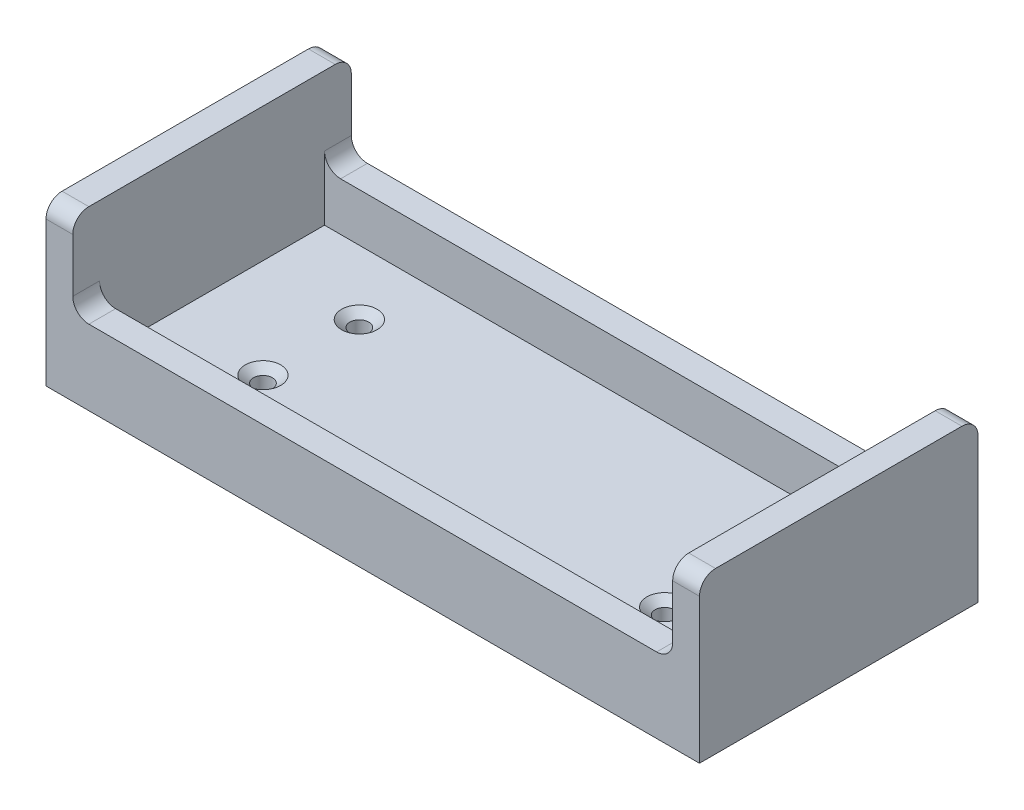
SolidWorks part; units mm, degrees
material "PET"
ref_plane "Front Plane" through (0, 0, 0) normal (0, 0, 1) x (1, 0, 0)
ref_plane "Top Plane" through (0, 0, 0) normal (0, 1, 0) x (1, 0, 0)
ref_plane "Right Plane" through (0, 0, 0) normal (1, 0, 0) x (0, 0, -1)
sketch "Sketch1" plane through (0, 0, 0) normal (0, 1, 0) x (1, 0, 0)
  line L0 (-69.4555, 22.0678) -> (-69.4555, 28.4178)
  line L5 (-69.4555, 22.0678) -> (72.7845, 22.0678)
  line L6 (-69.4555, 22.0678) -> (-69.4555, -31.2722)
  line L7 (-69.4555, -31.2722) -> (72.7845, -31.2722)
  line L8 (72.7845, 22.0678) -> (72.7845, -31.2722)
  line L9 (-75.8055, 28.4178) -> (79.1345, 28.4178)
  line L10 (-75.8055, 28.4178) -> (-75.8055, -37.6222)
  line L11 (-75.8055, -37.6222) -> (79.1345, -37.6222)
  line L12 (79.1345, 28.4178) -> (79.1345, -37.6222)
  line L13 (-69.4555, -31.2722) -> (-69.4555, -37.6222)
  line L14 (72.7845, 22.0678) -> (72.7845, 28.4178)
  line L15 (72.7845, -31.2722) -> (72.7845, -37.6222)
  point P0 (-49.1267, -9.4869)
  point P1 (-49.1267, 8.7015)
  point P2 (50.9319, 8.7015)
  point P3 (50.9319, -9.4869)
  point P8 (0, 0)
  dimension "D1" = 154.94
  dimension "D2" = 66.04
  dimension "D3" = 142.24
  dimension "D4" = 53.34
  dimension "D5" = 6.35
  dimension "D6" = 6.35
sketch "Sketch3" plane through (0, 0, 0) normal (0, 1, 0) x (1, 0, 0)
  line L1 (-69.4555, 22.0678) -> (72.7845, 22.0678)
  line L2 (-69.4555, 22.0678) -> (-69.4555, -31.2722)
  line L3 (-69.4555, -31.2722) -> (72.7845, -31.2722)
  line L4 (72.7845, 22.0678) -> (72.7845, -31.2722)
ref_plane "Plane2" through (72.39, 0, 0) normal (1, 0, 0) x (0, 0, -1)
extrude "Boss-Extrude1" add sketch "Sketch1" along normal blind 38.1 contours L8 L15 L11 L12 L9 L14 | L13 L6 L0 L9 L10 L11 region at (-72.6305, 0, 4.6022) region at (75.9595, 0, 4.6022)
extrude "Boss-Extrude2" add sketch "Sketch1<4>" along normal blind 6.35 contours L8 L5 L6 L7 region at (1.6645, 0, 4.6022)
sketch "Sketch1<4>" plane through (0, 0, 0) normal (0, 1, 0) x (1, 0, 0) same geometry as "Sketch1"
extrude "Boss-Extrude3" add sketch "Sketch1<5>" along normal blind 17.78 contours L5 L14 L9 L0 | L15 L7 L13 L11 region at (1.6645, 0, -25.2428) region at (1.6645, 0, 34.4472)
sketch "Sketch1<5>" plane through (0, 0, 0) normal (0, 1, 0) x (1, 0, 0) same geometry as "Sketch1"
fillet "Fillet1" radius 3.81 8 edges at (72.7845, 17.78, 34.4472) (72.7845, 17.78, -25.2428) (75.9595, 38.1, -28.4178) (75.9595, 38.1, 37.6222) (-72.6305, 38.1, -28.4178) (-69.4555, 17.78, -25.2428) (-69.4555, 17.78, 34.4472) (-72.6305, 38.1, 37.6222)
sketch "Sketch7" plane through (0, 6.35, 0) normal (0, 1, 0) x (1, 0, 0)
  line L2 (-75.8055, 24.6078) -> (-75.8055, -33.8122) construction
  line L5 (-65.6455, 28.4178) -> (68.9745, 28.4178) construction
  point P0 (-45.9605, 6.8278)
  point P1 (-45.9605, -16.0322)
  point P2 (49.2895, -16.0322)
  point P3 (49.2895, 6.8278)
  dimension "D1" = 22.86
  dimension "D2" = 22.86
  dimension "D3" = 95.25
  dimension "D4" = 95.25
  dimension "D5" = 29.845
  dimension "D6" = 21.59
  dimension "D7" = 21.59
hole_wizard "CSK for #8 Flat Head Machine Screw (100)2" positions "Sketch8" profile "Sketch9" countersink size "#8" standard "ANSI Inch" end condition through all
sketch "Sketch8" plane through (0, 6.35, 0) normal (0, 1, 0) x (1, 0, 0)
  point P0 (-45.9605, -16.0322)
  point P3 (-45.9605, 6.8278)
  point P6 (49.2895, 6.8278)
  point P9 (49.2895, -16.0322)
sketch "Sketch9" plane through (-45.9605, 6.35, 16.0322) normal (1, 0, 0) x (0, 0, 1)
  line L0 (0, 0) -> (0, 6.35)
  line L1 (0, 6.35) -> (2.2479, 6.35)
  line L2 (2.2479, 6.35) -> (2.2479, 1.6518)
  line L3 (2.2479, 1.6518) -> (4.2164, 0)
  line L5 (4.2164, 0) -> (0, 0)
  line L6 (-2.2479, 1.6518) -> (-4.2164, 0) construction
  line L11 (0, -6.35) -> (0, 107.95) construction
  dimension "Thru Hole Dia." = 4.4958
  dimension "Thru Hole Depth" = 6.35
  dimension "Near C'Sink Dia." = 8.4328
  dimension "Near C'Sink Angle" = 100
